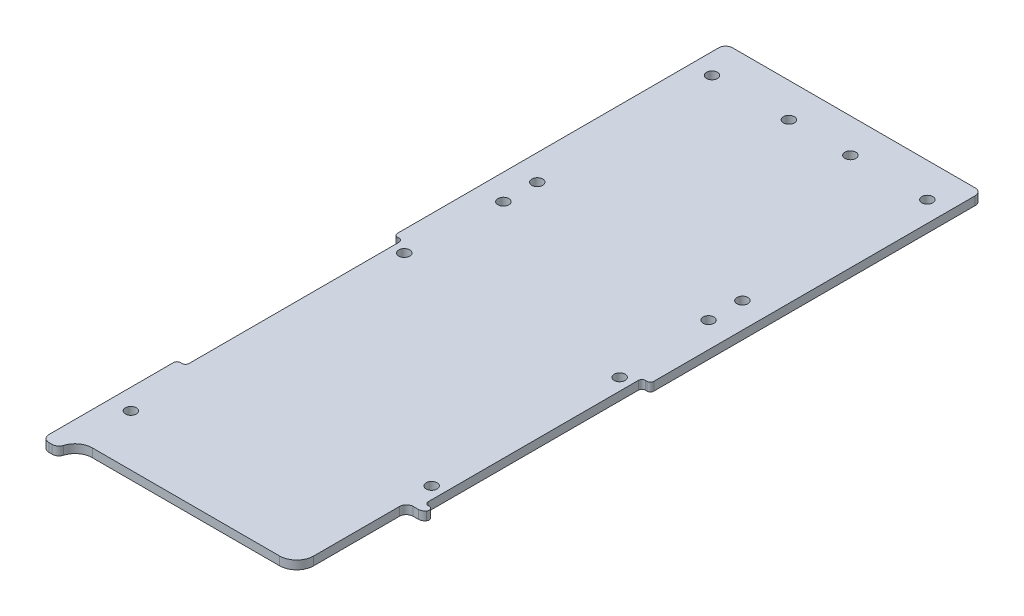
SolidWorks part; units mm, degrees
ref_plane "Front Plane" through (0, 0, 0) normal (0, 0, 1) x (1, 0, 0)
ref_plane "Top Plane" through (0, 0, 0) normal (0, 1, 0) x (1, 0, 0)
ref_plane "Right Plane" through (0, 0, 0) normal (1, 0, 0) x (0, 0, -1)
sketch "Sketch1" plane through (0, 0, 0) normal (0, 1, 0) x (1, 0, 0)
  line L0 (-39.9997, 0) -> (-39.9997, 114.3) construction
  line L1 (-47.625, 127) -> (47.625, 127)
  line L2 (-47.625, 127) -> (-47.625, -127)
  line L3 (-47.625, -127) -> (47.625, -127)
  line L4 (47.625, 127) -> (47.625, -127)
  line L5 (-47.625, 127) -> (47.625, -127) construction
  line L6 (-47.625, -127) -> (47.625, 127) construction
  line L7 (0, 0) -> (0, 127) construction
  line L8 (-39.9997, 0) -> (-39.9997, -101.6) construction
  line L9 (-39.9997, 0) -> (0, 0) construction
  line L10 (-41.275, -127) -> (-41.275, -120.65)
  line L11 (-41.275, -120.65) -> (41.275, -120.65)
  line L12 (41.275, -120.65) -> (41.275, -127)
  line L13 (-39.9997, 114.3) -> (-11.4247, 114.3) construction
  line L14 (39.9997, 114.3) -> (11.4247, 114.3) construction
  circle A0 centre (-39.9997, 114.3) radius 2.032
  circle A1 centre (-39.9997, 0) radius 2.032
  circle A2 centre (-39.9997, -101.6) radius 2.032
  circle A3 centre (39.9997, -101.6) radius 2.032
  circle A4 centre (39.9997, 0) radius 2.032
  circle A5 centre (39.9997, 114.3) radius 2.032
  circle A6 centre (-11.4247, 114.3) radius 2.032
  circle A7 centre (11.4247, 114.3) radius 2.032
  circle A8 centre (-39.9997, -69.85) radius 2.032
  circle A9 centre (39.9997, -69.85) radius 2.032
  point P0 (0, 0)
  dimension "D4" = 4.064
  dimension "D10" = 28.575
  dimension "D1" = 95.25
  dimension "D2" = 254
  dimension "D3" = 7.6253
  dimension "D5" = 12.7
  dimension "D6" = 25.4
  dimension "D7" = 6.35
  dimension "D8" = 6.35
  dimension "D9" = 6.35
  dimension "D11" = 69.85
extrude "Boss-Extrude1" add sketch "Sketch1" along normal blind 3.175 contours L4 L1 L2 L3 A4 A0 A1 A2 A3 A5 | A8 | A3 region at (0, 0, -2.6944) region at (39.9997, 0, 101.6) region at (-39.9997, 0, 69.85)
fillet "Fillet1" radius 2.54 4 edges at (-47.625, 1.5875, -127) (47.625, 1.5875, -127) (47.625, 1.5875, 127) (-47.625, 1.5875, 127)
fillet "Fillet2" radius 2.54 2 edges at (41.275, 1.5875, 127) (-41.275, 1.5875, 127)
fillet "Fillet3" radius 6.35 2 edges at (41.275, 1.5875, 120.65) (-41.275, 1.5875, 120.65)
sketch "Sketch2" plane through (0, 0, 0) normal (0, -1, 0) x (1, 0, 0)
  line L1 (43.815, 127) -> (45.085, 127) construction
  line L2 (40.6451, 123.5787) -> (40.6451, 79.8881)
  line L3 (40.6451, 79.8881) -> (47.625, 79.8881)
  line L11 (47.625, -124.46) -> (47.625, 124.46) construction
  line L12 (43.815, 127) -> (45.085, 127)
  line L13 (47.625, 79.8881) -> (47.625, 124.46)
  arc A0 (35.2956, 120.65) -> (41.3809, 125.1857) centre (35.2956, 127) ccw construction
  arc A1 (43.815, 127) -> (41.3809, 125.1857) centre (43.815, 124.46) ccw construction
  arc A2 (47.625, 124.46) -> (45.085, 127) centre (45.085, 124.46) ccw construction
  arc A3 (40.6451, 123.5787) -> (41.3809, 125.1857) centre (35.2956, 127) ccw
  arc A4 (43.815, 127) -> (41.3809, 125.1857) centre (43.815, 124.46) ccw
  arc A5 (47.625, 124.46) -> (45.085, 127) centre (45.085, 124.46) ccw
  dimension "D2" = 47.1119
  dimension "D1" = 6.9799
extrude "Cut-Extrude1" cut sketch "Sketch2" against normal through all
fillet "Fillet4" radius 6.35 1 edges at (40.6451, 1.5875, 123.5787)
fillet "Fillet5" radius 2.54 2 edges at (47.625, 1.5875, 79.8881) (40.6451, 1.5875, 79.8881)
sketch "Sketch3" plane through (0, 0, 0) normal (0, -1, 0) x (1, 0, 0)
  line L0 (-36.3023, -49.7791) -> (-39.9091, -49.7791) construction
  line L1 (-40.4171, -49.276) -> (-40.4171, -45.7043) construction
  line L2 (-35.7943, -45.7043) -> (-35.7943, -49.276) construction
  line L3 (-39.9091, -45.2013) -> (-36.3023, -45.2013) construction
  line L4 (-36.3023, -37.2027) -> (-39.9091, -37.2027) construction
  line L5 (-35.7943, -33.1279) -> (-35.7943, -36.6996) construction
  line L6 (-40.4171, -36.6996) -> (-40.4171, -33.1279) construction
  line L7 (-39.9091, -32.6249) -> (-36.3023, -32.6249) construction
  line L8 (36.2909, -32.6249) -> (39.8977, -32.6249) construction
  line L9 (40.4057, -33.1279) -> (40.4057, -36.6996) construction
  line L10 (39.8977, -37.2027) -> (36.2909, -37.2027) construction
  line L11 (35.7829, -36.6996) -> (35.7829, -33.1279) construction
  line L12 (36.2909, -45.2013) -> (39.8977, -45.2013) construction
  line L13 (35.7829, -49.276) -> (35.7829, -45.7043) construction
  line L14 (40.4057, -45.7043) -> (40.4057, -49.276) construction
  line L15 (39.8977, -49.7791) -> (36.2909, -49.7791) construction
  line L16 (-36.3023, -49.7791) -> (-39.9091, -49.7791)
  line L17 (-40.4171, -49.276) -> (-40.4171, -45.7043)
  line L18 (-35.7943, -45.7043) -> (-35.7943, -49.276)
  line L19 (-39.9091, -45.2013) -> (-36.3023, -45.2013)
  line L20 (-36.3023, -37.2027) -> (-39.9091, -37.2027)
  line L21 (-35.7943, -33.1279) -> (-35.7943, -36.6996)
  line L22 (-40.4171, -36.6996) -> (-40.4171, -33.1279)
  line L23 (-39.9091, -32.6249) -> (-36.3023, -32.6249)
  line L24 (36.2909, -32.6249) -> (39.8977, -32.6249)
  line L25 (40.4057, -33.1279) -> (40.4057, -36.6996)
  line L26 (39.8977, -37.2027) -> (36.2909, -37.2027)
  line L27 (35.7829, -36.6996) -> (35.7829, -33.1279)
  line L28 (36.2909, -45.2013) -> (39.8977, -45.2013)
  line L29 (35.7829, -49.276) -> (35.7829, -45.7043)
  line L30 (40.4057, -45.7043) -> (40.4057, -49.276)
  line L31 (39.8977, -49.7791) -> (36.2909, -49.7791)
  line L32 (-47.625, -25.836) -> (47.625, -25.836)
  line L33 (-47.625, -124.46) -> (-47.625, 124.46) construction
  line L34 (47.625, -124.46) -> (47.625, 77.3481) construction
  line L35 (0, -25.836) -> (0, -56.0686) construction
  line L1362 (-40.4171, -34.9138) -> (-35.7943, -34.9138)
  line L1857 (-38.1057, -32.6249) -> (-38.1057, -37.2027)
  line L1858 (-38.1057, -45.2013) -> (-38.1057, -49.7791)
  line L1859 (-40.4171, -47.4902) -> (-35.7943, -47.4902)
  circle A0 centre (-38.1057, -34.9138) radius 2.032
  circle A1 centre (-38.1057, -47.4902) radius 2.032
  circle A2 centre (38.1057, -47.4902) radius 2.032
  circle A3 centre (38.1057, -34.9138) radius 2.032
  ellipse E0 centre (-39.9091, -45.7043) end of major axis (-39.4011, -45.7043) minor radius 0.5031 (-39.9091, -45.2013) -> (-40.4171, -45.7043) ccw construction
  ellipse E1 centre (-39.9091, -49.276) end of major axis (-39.4011, -49.276) minor radius 0.5031 (-40.4171, -49.276) -> (-39.9091, -49.7791) ccw construction
  ellipse E6 centre (-36.3023, -49.276) end of major axis (-35.7943, -49.276) minor radius 0.5031 (-36.3023, -49.7791) -> (-35.7943, -49.276) ccw construction
  ellipse E7 centre (-36.3023, -45.7043) end of major axis (-35.7943, -45.7043) minor radius 0.5031 (-35.7943, -45.7043) -> (-36.3023, -45.2013) ccw construction
  ellipse E8 centre (-39.9091, -36.6996) end of major axis (-39.4011, -36.6996) minor radius 0.5031 (-40.4171, -36.6996) -> (-39.9091, -37.2027) ccw construction
  ellipse E9 centre (-36.3023, -36.6996) end of major axis (-35.7943, -36.6996) minor radius 0.5031 (-36.3023, -37.2027) -> (-35.7943, -36.6996) ccw construction
  ellipse E10 centre (-36.3023, -33.1279) end of major axis (-35.7943, -33.1279) minor radius 0.5031 (-35.7943, -33.1279) -> (-36.3023, -32.6249) ccw construction
  ellipse E11 centre (-39.9091, -33.1279) end of major axis (-39.4011, -33.1279) minor radius 0.5031 (-39.9091, -32.6249) -> (-40.4171, -33.1279) ccw construction
  ellipse E12 centre (39.8977, -33.1279) end of major axis (40.4057, -33.1279) minor radius 0.5031 (40.4057, -33.1279) -> (39.8977, -32.6249) ccw construction
  ellipse E13 centre (36.2909, -33.1279) end of major axis (36.7989, -33.1279) minor radius 0.5031 (36.2909, -32.6249) -> (35.7829, -33.1279) ccw construction
  ellipse E14 centre (39.8977, -36.6996) end of major axis (40.4057, -36.6996) minor radius 0.5031 (39.8977, -37.2027) -> (40.4057, -36.6996) ccw construction
  ellipse E15 centre (36.2909, -36.6996) end of major axis (36.7989, -36.6996) minor radius 0.5031 (35.7829, -36.6996) -> (36.2909, -37.2027) ccw construction
  ellipse E16 centre (36.2909, -45.7043) end of major axis (36.7989, -45.7043) minor radius 0.5031 (36.2909, -45.2013) -> (35.7829, -45.7043) ccw construction
  ellipse E17 centre (36.2909, -49.276) end of major axis (36.7989, -49.276) minor radius 0.5031 (35.7829, -49.276) -> (36.2909, -49.7791) ccw construction
  ellipse E18 centre (39.8977, -45.7043) end of major axis (40.4057, -45.7043) minor radius 0.5031 (40.4057, -45.7043) -> (39.8977, -45.2013) ccw construction
  ellipse E19 centre (39.8977, -49.276) end of major axis (40.4057, -49.276) minor radius 0.5031 (39.8977, -49.7791) -> (40.4057, -49.276) ccw construction
  ellipse E20 centre (-39.9091, -45.7043) end of major axis (-39.4011, -45.7043) minor radius 0.5031 (-39.9091, -45.2013) -> (-40.4171, -45.7043) ccw
  ellipse E21 centre (-39.9091, -49.276) end of major axis (-39.4011, -49.276) minor radius 0.5031 (-40.4171, -49.276) -> (-39.9091, -49.7791) ccw
  ellipse E22 centre (-36.3023, -49.276) end of major axis (-35.7943, -49.276) minor radius 0.5031 (-36.3023, -49.7791) -> (-35.7943, -49.276) ccw
  ellipse E23 centre (-36.3023, -45.7043) end of major axis (-35.7943, -45.7043) minor radius 0.5031 (-35.7943, -45.7043) -> (-36.3023, -45.2013) ccw
  ellipse E24 centre (-39.9091, -36.6996) end of major axis (-39.4011, -36.6996) minor radius 0.5031 (-40.4171, -36.6996) -> (-39.9091, -37.2027) ccw
  ellipse E25 centre (-36.3023, -36.6996) end of major axis (-35.7943, -36.6996) minor radius 0.5031 (-36.3023, -37.2027) -> (-35.7943, -36.6996) ccw
  ellipse E26 centre (-36.3023, -33.1279) end of major axis (-35.7943, -33.1279) minor radius 0.5031 (-35.7943, -33.1279) -> (-36.3023, -32.6249) ccw
  ellipse E27 centre (-39.9091, -33.1279) end of major axis (-39.4011, -33.1279) minor radius 0.5031 (-39.9091, -32.6249) -> (-40.4171, -33.1279) ccw
  ellipse E28 centre (39.8977, -33.1279) end of major axis (40.4057, -33.1279) minor radius 0.5031 (40.4057, -33.1279) -> (39.8977, -32.6249) ccw
  ellipse E29 centre (36.2909, -33.1279) end of major axis (36.7989, -33.1279) minor radius 0.5031 (36.2909, -32.6249) -> (35.7829, -33.1279) ccw
  ellipse E30 centre (39.8977, -36.6996) end of major axis (40.4057, -36.6996) minor radius 0.5031 (39.8977, -37.2027) -> (40.4057, -36.6996) ccw
  ellipse E31 centre (36.2909, -36.6996) end of major axis (36.7989, -36.6996) minor radius 0.5031 (35.7829, -36.6996) -> (36.2909, -37.2027) ccw
  ellipse E32 centre (36.2909, -45.7043) end of major axis (36.7989, -45.7043) minor radius 0.5031 (36.2909, -45.2013) -> (35.7829, -45.7043) ccw
  ellipse E33 centre (36.2909, -49.276) end of major axis (36.7989, -49.276) minor radius 0.5031 (35.7829, -49.276) -> (36.2909, -49.7791) ccw
  ellipse E34 centre (39.8977, -45.7043) end of major axis (40.4057, -45.7043) minor radius 0.5031 (40.4057, -45.7043) -> (39.8977, -45.2013) ccw
  ellipse E35 centre (39.8977, -49.276) end of major axis (40.4057, -49.276) minor radius 0.5031 (39.8977, -49.7791) -> (40.4057, -49.276) ccw
  dimension "D2" = 4.064
extrude "Cut-Extrude2" cut sketch "Sketch3" against normal through all contours A0 | A1 | A2 | A3
sketch "Sketch4" plane through (0, 3.175, 0) normal (0, 1, 0) x (1, 0, 0)
  line L11 (-47.625, 124.46) -> (-47.625, -124.46) construction
  line L12 (-47.625, -76.835) -> (-44.45, -76.835)
  line L13 (-47.625, -76.835) -> (-47.625, 3.81)
  line L15 (-47.625, 3.81) -> (-44.45, 3.81)
  line L16 (-44.45, -76.835) -> (-44.45, 3.81)
  line L17 (47.625, 124.46) -> (47.625, -77.3481) construction
  line L18 (47.625, -76.835) -> (44.45, -76.835)
  line L19 (47.625, -76.835) -> (47.625, 3.81)
  line L20 (47.625, 3.81) -> (44.45, 3.81)
  line L45 (44.45, -76.835) -> (44.45, 3.81)
  line L47 (43.1851, -79.8881) -> (45.085, -79.8881) construction
  dimension "D1" = 3.175
  dimension "D2" = 80.645
  dimension "D3" = 3.0531
extrude "Cut-Extrude3" cut sketch "Sketch4" against normal through all and the other way through all
fillet "Fillet6" radius 1.27 8 edges at (-44.45, 1.5875, -3.81) (-47.625, 1.5875, -3.81) (-47.625, 1.5875, 76.835) (-44.45, 1.5875, 76.835) (44.45, 1.5875, 76.835) (47.625, 1.5875, 76.835) (44.45, 1.5875, -3.81) (47.625, 1.5875, -3.81)
